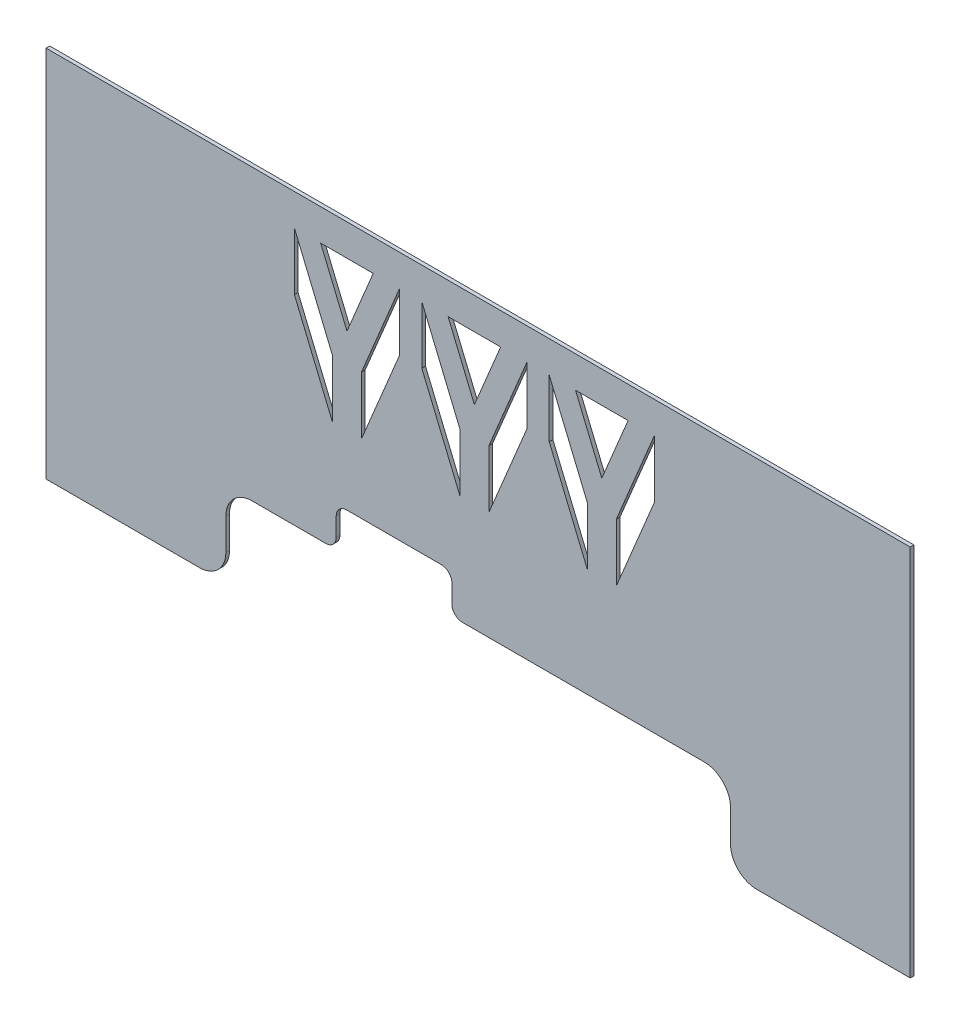
SolidWorks part; units mm, degrees
ref_plane "Front Plane" through (0, 0, 0) normal (0, 0, 1) x (1, 0, 0)
ref_plane "Top Plane" through (0, 0, 0) normal (0, 1, 0) x (1, 0, 0)
ref_plane "Right Plane" through (0, 0, 0) normal (1, 0, 0) x (0, 0, -1)
sketch "Sketch1" plane through (0, 0, 0) normal (0, 0, 1) x (1, 0, 0)
  line L0 (25.5163, 100.6601) -> (25.5163, -39.2092) construction
  line L1 (0, 0) -> (164.384, 0)
  line L2 (0, 0) -> (0, 71)
  line L3 (0, 71) -> (164.384, 71)
  line L4 (164.384, 0) -> (164.384, 71)
  line L16 (15.5163, 98.1307) -> (15.5163, -13.2298) construction
  line L17 (10.5163, 65) -> (20.5163, 65)
  line L18 (20.5163, 65) -> (15.5163, 53)
  line L19 (15.5163, 53) -> (10.5163, 65)
  line L20 (25.5163, 65) -> (25.5163, 54)
  line L21 (25.5163, 54) -> (18.2663, 36.6)
  line L22 (18.2663, 36.6) -> (18.2663, 47.6)
  line L23 (18.2663, 47.6) -> (25.5163, 65)
  line L24 (5.5163, 65) -> (12.7663, 47.6)
  line L25 (12.7663, 47.6) -> (12.7663, 36.6)
  line L26 (12.7663, 36.6) -> (5.5163, 54)
  line L27 (5.5163, 54) -> (5.5163, 65)
  line L28 (47.2334, 110.9264) -> (47.2334, -39.2092) construction
  line L29 (52.2334, 65) -> (62.2334, 65)
  line L30 (54.4834, 47.6) -> (54.4834, 36.6)
  line L31 (62.2334, 65) -> (57.2334, 53)
  line L32 (67.2334, 54) -> (59.9834, 36.6)
  line L33 (54.4834, 36.6) -> (47.2334, 54)
  line L34 (57.2334, 53) -> (52.2334, 65)
  line L35 (47.2334, 54) -> (47.2334, 65)
  line L36 (59.9834, 36.6) -> (59.9834, 47.6)
  line L37 (59.9834, 47.6) -> (67.2334, 65)
  line L38 (47.2334, 65) -> (54.4834, 47.6)
  line L39 (67.2334, 65) -> (67.2334, 54)
  line L40 (78.7224, 47.6) -> (78.7224, 36.6)
  line L41 (78.7224, 36.6) -> (71.4724, 54)
  line L42 (71.4724, 54) -> (71.4724, 65)
  line L43 (71.4724, 65) -> (78.7224, 47.6)
  line L44 (91.4724, 54) -> (84.2224, 36.6)
  line L45 (84.2224, 36.6) -> (84.2224, 47.6)
  line L46 (84.2224, 47.6) -> (91.4724, 65)
  line L47 (91.4724, 65) -> (91.4724, 54)
  line L48 (76.4724, 65) -> (86.4724, 65)
  line L49 (86.4724, 65) -> (81.4724, 53)
  line L50 (81.4724, 53) -> (76.4724, 65)
  line L51 (102.9614, 47.6) -> (102.9614, 36.6)
  line L52 (102.9614, 36.6) -> (95.7114, 54)
  line L53 (95.7114, 54) -> (95.7114, 65)
  line L54 (95.7114, 65) -> (102.9614, 47.6)
  line L55 (115.7114, 54) -> (108.4614, 36.6)
  line L56 (108.4614, 36.6) -> (108.4614, 47.6)
  line L57 (108.4614, 47.6) -> (115.7114, 65)
  line L58 (115.7114, 65) -> (115.7114, 54)
  line L59 (100.7114, 65) -> (110.7114, 65)
  line L60 (110.7114, 65) -> (105.7114, 53)
  line L61 (105.7114, 53) -> (100.7114, 65)
  line L62 (138.8676, 110.9264) -> (138.8676, -39.2092) construction
  line L63 (159.2989, 65) -> (159.2989, 54)
  line L64 (146.1176, 36.6) -> (138.8676, 54)
  line L65 (138.8676, 65) -> (146.1176, 47.6)
  line L66 (152.0489, 36.6) -> (152.0489, 47.6)
  line L67 (149.2989, 53) -> (144.2989, 65)
  line L68 (144.2989, 65) -> (154.2989, 65)
  line L69 (146.1176, 47.6) -> (146.1176, 36.6)
  line L70 (138.8676, 54) -> (138.8676, 65)
  line L71 (152.0489, 47.6) -> (159.2989, 65)
  line L72 (159.2989, 54) -> (152.0489, 36.6)
  line L73 (154.2989, 65) -> (149.2989, 53)
  line L74 (82.192, 71) -> (82.192, 0) construction
  line L75 (77.192, 16) -> (130.192, 16)
  line L76 (34.192, 16) -> (55.192, 16)
  line L77 (34.192, 16) -> (34.192, 0)
  line L78 (34.192, 0) -> (130.192, 0)
  line L79 (130.192, 16) -> (130.192, 0)
  line L80 (34.192, 16) -> (130.192, 0) construction
  line L81 (34.192, 0) -> (130.192, 16) construction
  line L83 (55.192, 16) -> (55.192, 23.5)
  line L84 (55.192, 23.5) -> (77.192, 23.5)
  line L85 (77.192, 16) -> (77.192, 23.5)
  line L86 (15.5163, 53.65) -> (10.8913, 64.75)
  line L87 (10.8913, 64.75) -> (20.1413, 64.75)
  line L88 (20.1413, 64.75) -> (15.5163, 53.65)
  line L89 (5.7663, 54.05) -> (5.7663, 63.75)
  line L90 (5.7663, 63.75) -> (12.5163, 47.55)
  line L91 (12.5163, 47.55) -> (12.5163, 37.85)
  line L92 (12.5163, 37.85) -> (5.7663, 54.05)
  line L93 (18.5163, 47.55) -> (25.2663, 63.75)
  line L94 (25.2663, 63.75) -> (25.2663, 54.05)
  line L95 (25.2663, 54.05) -> (18.5163, 37.85)
  line L96 (18.5163, 37.85) -> (18.5163, 47.55)
  line L97 (149.2989, 53.65) -> (144.6739, 64.75)
  line L98 (144.6739, 64.75) -> (153.9239, 64.75)
  line L99 (153.9239, 64.75) -> (149.2989, 53.65)
  line L100 (145.8676, 37.85) -> (139.1176, 54.05)
  line L101 (139.1176, 54.05) -> (139.1176, 63.75)
  line L102 (139.1176, 63.75) -> (145.8676, 47.55)
  line L103 (145.8676, 47.55) -> (145.8676, 37.85)
  line L104 (159.0489, 63.75) -> (159.0489, 54.05)
  line L105 (159.0489, 54.05) -> (152.2989, 37.85)
  line L106 (152.2989, 37.85) -> (152.2989, 47.55)
  line L107 (152.2989, 47.55) -> (159.0489, 63.75)
  point P12 (15.5163, 65)
  point P26 (57.2291, 65)
  point P62 (149.3282, 65)
  point P75 (82.192, 8)
  dimension "D1" = 164.384
  dimension "D2" = 71
  dimension "D3" = 25.5163
  dimension "D4" = 10
  dimension "D5" = 10
  dimension "D6" = 12
  dimension "D7" = 6
  dimension "D8" = 11
  dimension "D9" = 28.4
  dimension "D10" = 28.4
  dimension "D11" = 5
  dimension "D12" = 2.75
  dimension "D13" = 2.75
  dimension "D14" = 47.2334
  dimension "D15" = 0
  dimension "D16" = 5
  dimension "D17" = 3
  dimension "D18" = 25.5163
  dimension "D19" = 0
  dimension "D20" = 96
  dimension "D21" = 55
  dimension "D22" = 22
  dimension "D23" = 7.5
  dimension "D24" = 5
  dimension "D25" = 0.25
extrude "Boss-Extrude1" add sketch "Sketch1" along normal blind 0.7 contours L23 L22 L21 L20 | L19 L18 L17 | L27 L26 L25 L24 | L73 L68 L67 | L85 L75 L79 L1 L4 L3 L2 L77 L76 L83 L84 L18 L19 L17 L22 L23 L20 L21 L26 L27 L24 L25 L31 L34 L29 L35 L38 L30 L33 L37 L39 L32 L36 L42 L43 L40 L41 L46 L47 L44 L45 | L72 L63 L71 L66 | L70 L64 L69 L65 | L93 L94 L95 L96 | L86 L87 L88 | L89 L90 L91 L92 | L97 L98 L99 | L100 L101 L102 L103 | L104 L105 L106 L107 region at (82.5361, 38.3161, 0) region at (15.5163, 64.8438, 0) region at (25.487, 59.5, 0) region at (9.1143, 56.2887, 0) region at (159.2696, 59.5, 0) region at (142.5197, 45.3113, 0) region at (146.9431, 59.0601, 0)
extrude "Boss-Extrude2" add sketch "Sketch1<4>" against normal blind 5 contours L99 L98 L97 | L103 L102 L101 L100 | L107 L106 L105 L104 | L88 L87 L86 | L92 L91 L90 L89 | L96 L95 L94 L93 region at (15.5163, 61.05, 0) region at (9.1413, 50.8, 0) region at (21.8913, 50.8, 0) region at (149.2989, 61.05, 0) region at (142.4926, 50.8, 0) region at (155.6739, 50.8, 0)
sketch "Sketch1<4>" plane through (0, 0, 0) normal (0, 0, 1) x (1, 0, 0) same geometry as "Sketch1"
fillet "Fillet1" radius 5 4 edges at (130.192, 16, 0.35) (130.192, 0, 0.35) (34.192, 0, 0.35) (34.192, 16, 0.35)
fillet "Fillet2" radius 2 4 edges at (77.192, 16, 0.35) (77.192, 23.5, 0.35) (55.192, 16, 0.35) (55.192, 23.5, 0.35)
